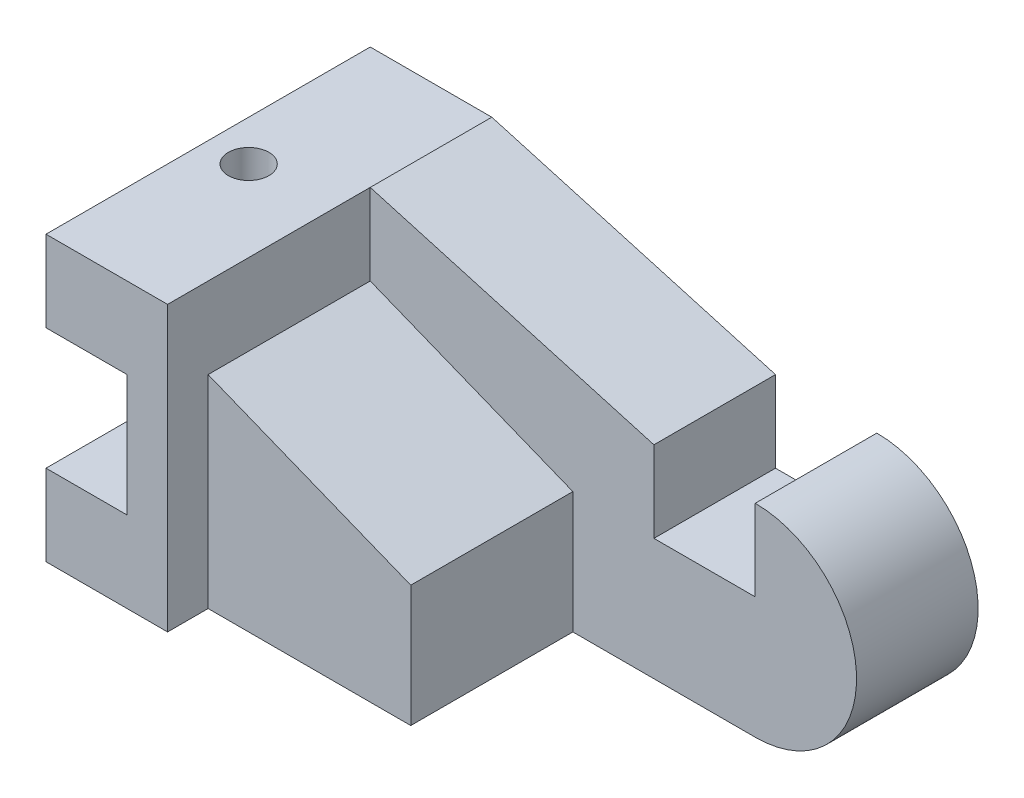
SolidWorks part; units mm, degrees
ref_plane "Front Plane" through (0, 0, 0) normal (0, 0, 1) x (1, 0, 0)
ref_plane "Top Plane" through (0, 0, 0) normal (0, 1, 0) x (1, 0, 0)
ref_plane "Right Plane" through (0, 0, 0) normal (1, 0, 0) x (0, 0, -1)
sketch "Sketch1" plane through (0, 0, 0) normal (0, 0, 1) x (1, 0, 0)
  line L0 (0, 0) -> (63441.6479, 0) construction
  line L1 (0, 0) -> (0, 63441.6479) construction
  line L2 (-30, 70) -> (-30, 50)
  line L3 (-30, 50) -> (-10, 50)
  line L4 (-10, 50) -> (-10, 20)
  line L5 (-10, 20) -> (-30, 20)
  line L6 (-30, 20) -> (-30, 0)
  line L7 (-30, 0) -> (0, 0)
  line L8 (0, 0) -> (0, 70)
  line L9 (0, 70) -> (-30, 70)
  line L10 (0, 0) -> (95, 0)
  line L11 (95, 50) -> (95, 30)
  line L12 (95, 30) -> (70, 30)
  line L13 (70, 30) -> (70, 50)
  line L14 (70, 50) -> (0, 70)
  arc A0 (95, 0) -> (95, 50) centre (95, 25) ccw
  point P18 (0, 0)
  point P20 (0, 0)
  point P21 (-76.2821, 43.9744)
  point P22 (0, 0)
  point P23 (0, 0)
  dimension "D1" = 20
  dimension "D6" = 25
  dimension "D2" = 70
  dimension "D3" = 20
  dimension "D4" = 30
  dimension "D5" = 95
  dimension "D7" = 20
  dimension "D8" = 5
  dimension "D9" = 70
extrude "Boss-Extrude1" add sketch "Sketch1" along normal mid plane 80 contours L8 L9 L2 L3 L4 L5 L6 L7 region at (-15, 69.2384, 0)
extrude "Boss-Extrude2" add sketch "Sketch1<3>" along normal blind 30 from offset 40 contours L10 A0 L11 L12 L13 L14 L8 region at (51.3156, 27.4726, 0) offset against normal yes
sketch "Sketch1<3>" plane through (0, 0, 0) normal (0, 0, 1) x (1, 0, 0) same geometry as "Sketch1"
sketch "Sketch2" plane through (0, 0, -10) normal (0, 0, 1) x (1, 0, 0)
  line L0 (0, 50) -> (0, 0)
  line L1 (0, 0) -> (0, 70) construction
  line L2 (0, 0) -> (50, 0)
  line L3 (0, 0) -> (95, 0) construction
  line L4 (50, 0) -> (50, 30)
  line L5 (50, 30) -> (0, 50)
  point P8 (0, 0)
  dimension "D1" = 50
  dimension "D2" = 50
extrude "Boss-Extrude3" add sketch "Sketch2" along normal blind 40
hole_wizard "Ø10.0mm Dowel Hole1" positions "Sketch3" profile "Sketch4" hole size "Ø10.0" standard "ANSI Metric" end condition up to next
sketch "Sketch3" plane through (0, 70, 0) normal (0, 1, 0) x (1, 0, 0)
  line L0 (-30, -40) -> (-30, 40) construction
  line L1 (0, 40) -> (-30, 40) construction
  point P0 (-20, 0)
  dimension "D1" = 10
  dimension "D2" = 40
sketch "Sketch4" plane through (-20, 70, 0) normal (1, 0, 0) x (0, 0, 1)
  line L0 (0, 0) -> (0, 20)
  line L1 (0, 20) -> (5, 20)
  line L2 (5, 20) -> (5, 0)
  line L5 (5, 0) -> (0, 0)
  line L11 (0, -6.35) -> (0, 107.95) construction
  dimension "Thru Hole Dia." = 10
  dimension "Thru Hole Depth" = 20
